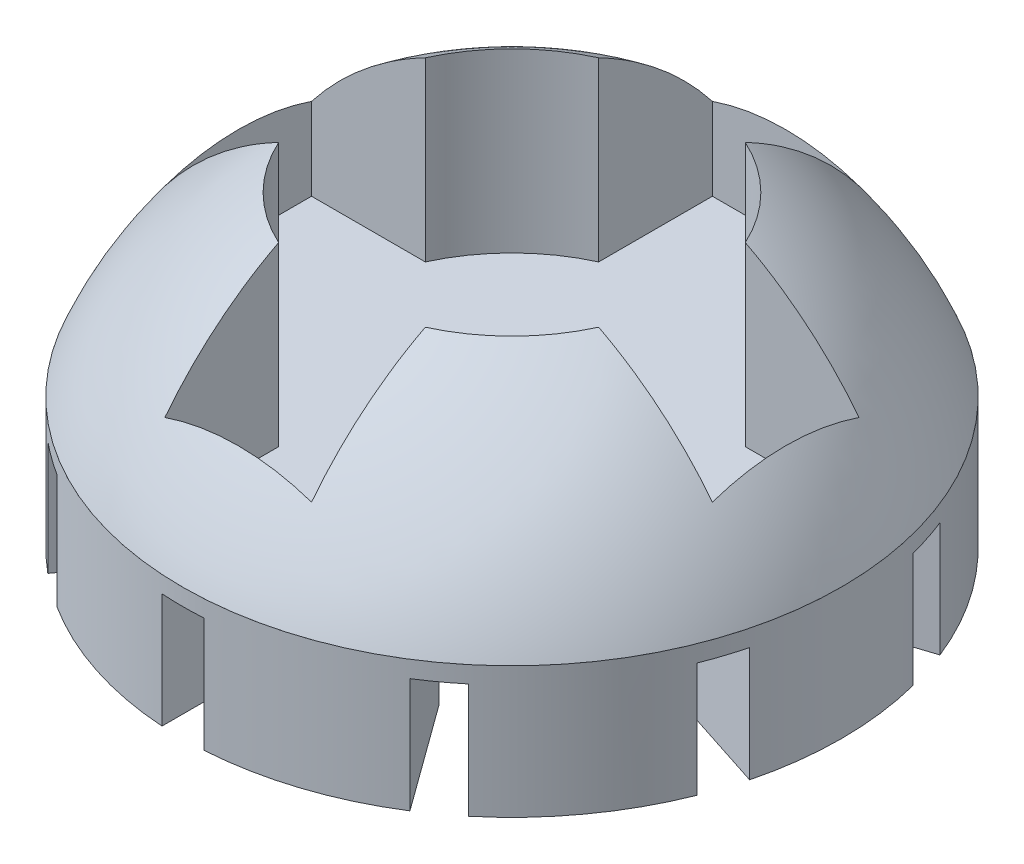
SolidWorks part; units mm, degrees
ref_plane "Front Plane" through (0, 0, 0) normal (0, 0, 1) x (1, 0, 0)
ref_plane "Top Plane" through (0, 0, 0) normal (0, 1, 0) x (1, 0, 0)
ref_plane "Right Plane" through (0, 0, 0) normal (1, 0, 0) x (0, 0, -1)
sketch "Sketch1" plane through (0, 0, 0) normal (0, 1, 0) x (1, 0, 0)
  circle A0 centre (0, 0) radius 29.972
  circle A1 centre (0, 0) radius 5.5562
  dimension "D1" = 59.944
  dimension "D2" = 11.1125
extrude "Boss-Extrude1" add sketch "Sketch1" along normal blind 11.938
sketch "Sketch2" plane through (0, 0, 0) normal (0, 0, 1) x (1, 0, 0)
  line L0 (5.5562, 11.938) -> (-5.5562, 11.938) construction
  line L1 (0, 11.938) -> (29.972, 11.938)
  line L2 (0, 32.262) -> (0, 11.938)
  line L3 (0, 49.3155) -> (0, -18.7616) construction
  arc A1 (29.972, 11.938) -> (0, 32.262) centre (0, 0) ccw
revolve "Revolve1" add sketch "Sketch2" angle 360 about L3
sketch "Sketch3" plane through (0, 11.938, 0) normal (0, 1, 0) x (1, 0, 0)
  line L0 (0, 24.892) -> (0, -24.892) construction
  line L1 (0, 29.972) -> (0, -29.972) construction
  circle A0 centre (0, 0) radius 29.972 construction
  line B0 (-6.6675, 14.5468) -> (-6.6675, 24.892)
  line B1 (-6.6675, -24.892) -> (6.6675, -24.892)
  line B2 (-6.6675, -24.892) -> (-6.6675, -14.5468)
  line B3 (-6.6675, 24.892) -> (6.6675, 24.892)
  line B4 (6.6675, -24.892) -> (6.6675, -14.5468)
  line B5 (-6.6675, -24.892) -> (6.6675, 24.892) construction
  line B6 (-6.6675, 24.892) -> (6.6675, -24.892) construction
  line B7 (-24.892, -6.6675) -> (-14.5468, -6.6675)
  line B8 (-24.892, -6.6675) -> (-24.892, 6.6675)
  line B9 (-24.892, 6.6675) -> (-14.5468, 6.6675)
  line B10 (24.892, -6.6675) -> (24.892, 6.6675)
  line B11 (-24.892, -6.6675) -> (24.892, 6.6675) construction
  line B12 (-24.892, 6.6675) -> (24.892, -6.6675) construction
  line B13 (6.6675, 14.5468) -> (6.6675, 24.892)
  line B14 (14.5468, -6.6675) -> (24.892, -6.6675)
  line B15 (14.5468, 6.6675) -> (24.892, 6.6675)
  arc B16 (-6.6675, 14.5468) -> (-14.5468, 6.6675) centre (0, 0) ccw
  arc B17 (-14.5468, -6.6675) -> (-6.6675, -14.5468) centre (0, 0) ccw
  arc B18 (6.6675, -14.5468) -> (14.5468, -6.6675) centre (0, 0) ccw
  arc B19 (14.5468, 6.6675) -> (6.6675, 14.5468) centre (0, 0) ccw
sketch_block_instance "Block1-1"
sketch_block "Block1" parameters "D1"=32.004, "D2"=49.784, "D3"=13.335
extrude "Cut-Extrude1" cut sketch "Sketch3" along normal through all
sketch "Sketch4" plane through (0, 0, 0) normal (0, -1, 0) x (-1, 0, 0)
  line L3 (1.905, -31.2263) -> (-1.905, -31.2263)
  line L7 (-16.8132, -26.3823) -> (-19.8955, -24.1429)
  line L12 (-29.1093, -11.4612) -> (-30.2867, -7.8377)
  line L17 (-30.2867, 7.8377) -> (-29.1093, 11.4612)
  line L22 (-19.8955, 24.1429) -> (-16.8132, 26.3823)
  line L27 (-1.905, 31.2263) -> (1.905, 31.2263)
  line L32 (16.8132, 26.3823) -> (19.8955, 24.1429)
  line L37 (29.1093, 11.4612) -> (30.2867, 7.8377)
  line L42 (30.2867, -7.8377) -> (29.1093, -11.4612)
  line L47 (19.8955, -24.1429) -> (16.8132, -26.3823)
  line L51 (-12.082, -13.3885) -> (-19.8955, -24.1429)
  line L53 (-8.9996, -15.6279) -> (-16.8132, -26.3823)
  line L54 (-1.905, -17.9331) -> (-1.905, -31.2263)
  line L57 (1.905, -17.9331) -> (1.905, -31.2263)
  line L58 (8.9996, -15.6279) -> (16.8132, -26.3823)
  line L60 (12.082, -13.3885) -> (19.8955, -24.1429)
  line L61 (16.4667, -7.3534) -> (29.1093, -11.4612)
  line L63 (17.6441, -3.7299) -> (30.2867, -7.8377)
  line L64 (17.6441, 3.7299) -> (30.2867, 7.8377)
  line L66 (16.4667, 7.3534) -> (29.1093, 11.4612)
  line L67 (12.082, 13.3885) -> (19.8955, 24.1429)
  line L69 (8.9996, 15.6279) -> (16.8132, 26.3823)
  line L70 (1.905, 17.9331) -> (1.905, 31.2263)
  line L72 (-1.905, 17.9331) -> (-1.905, 31.2263)
  line L73 (-8.9996, 15.6279) -> (-16.8132, 26.3823)
  line L75 (-12.082, 13.3885) -> (-19.8955, 24.1429)
  line L76 (-16.4667, 7.3534) -> (-29.1093, 11.4612)
  line L78 (-17.6441, 3.7299) -> (-30.2867, 7.8377)
  line L79 (-17.6441, -3.7299) -> (-30.2867, -7.8377)
  line L81 (-16.4667, -7.3534) -> (-29.1093, -11.4612)
  arc A0 (12.082, -13.3885) -> (16.4667, -7.3534) centre (0, 0) ccw
  arc A1 (1.905, -17.9331) -> (8.9996, -15.6279) centre (0, 0) ccw
  arc A2 (-8.9996, -15.6279) -> (-1.905, -17.9331) centre (0, 0) ccw
  arc A3 (-16.4667, -7.3534) -> (-12.082, -13.3885) centre (0, 0) ccw
  arc A4 (-17.6441, 3.7299) -> (-17.6441, -3.7299) centre (0, 0) ccw
  arc A5 (-12.082, 13.3885) -> (-16.4667, 7.3534) centre (0, 0) ccw
  arc A6 (-1.905, 17.9331) -> (-8.9996, 15.6279) centre (0, 0) ccw
  arc A7 (8.9996, 15.6279) -> (1.905, 17.9331) centre (0, 0) ccw
  arc A8 (16.4667, 7.3534) -> (12.082, 13.3885) centre (0, 0) ccw
  arc A9 (17.6441, -3.7299) -> (17.6441, 3.7299) centre (0, 0) ccw
  point P3 (0, -18.034)
  dimension "D1" = 36.068
  dimension "D2" = 3.81
  dimension "D3" = 10
extrude "Cut-Extrude2" cut sketch "Sketch4" against normal blind 10.414
